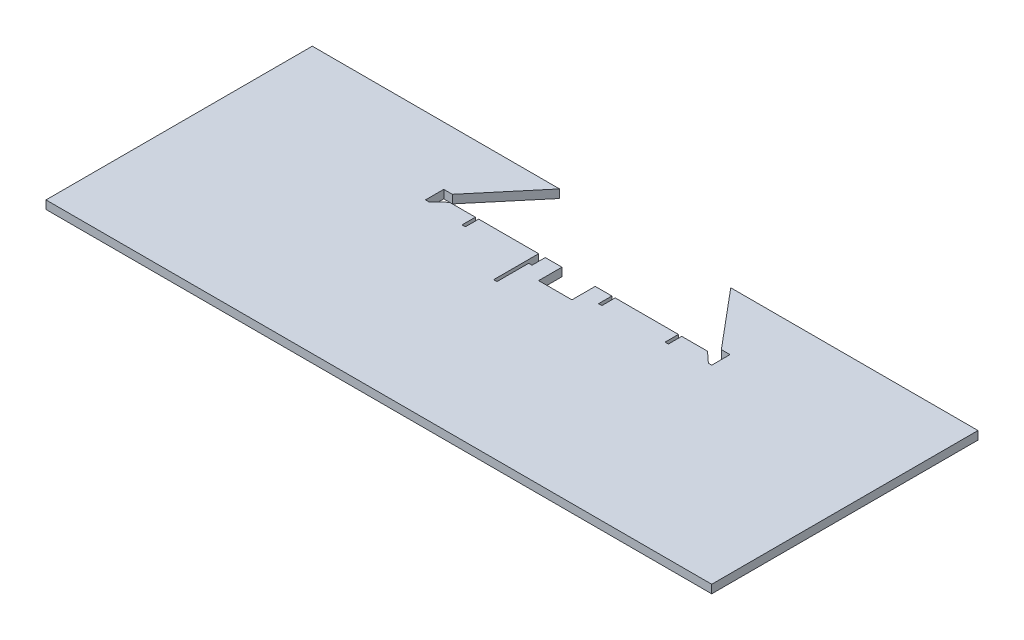
SolidWorks part; units mm, degrees
material "Depron"
ref_plane "Front Plane" through (0, 0, 0) normal (0, 0, 1) x (1, 0, 0)
ref_plane "Top Plane" through (0, 0, 0) normal (0, 1, 0) x (1, 0, 0)
ref_plane "Right Plane" through (0, 0, 0) normal (1, 0, 0) x (0, 0, -1)
sketch "Sketch1" plane through (0, 0, 0) normal (0, 1, 0) x (1, 0, 0)
  line L0 (32.6619, 101.6) -> (127, 101.6)
  line L1 (-127, 0) -> (127, 0)
  line L2 (-127, 0) -> (-127, 101.6)
  line L3 (-127, 101.6) -> (-32.6619, 101.6)
  line L4 (127, 0) -> (127, 101.6)
  line L5 (0, -898.4) -> (0, 49101.6) construction
  line L6 (-53.975, 76.2) -> (-32.6619, 101.6)
  line L7 (-53.975, 76.2) -> (53.975, 76.2)
  line L8 (53.975, 76.2) -> (32.6619, 101.6)
  line L9 (-1003.9539, 76.2) -> (48996.0461, 76.2) construction
  point P11 (0, 76.2)
  dimension "D1" = 101.6
  dimension "D2" = 254
  dimension "D4" = 107.95
  dimension "D6" = 25.4
extrude "Boss-Extrude1" add sketch "Sketch1" along normal blind 3.175
sketch "Sketch2" plane through (0, 3.175, 0) normal (0, 1, 0) x (-1, 0, 0)
  line L0 (0, 0) -> (0, -134.62) construction
  line L1 (127, 0) -> (-127, 0) construction
  line L2 (-53.975, -76.2) -> (53.975, -76.2) construction
  line L3 (39.37, -76.2) -> (38.1, -76.2)
  line L4 (39.37, -76.2) -> (39.37, -71.12)
  line L5 (39.37, -71.12) -> (38.1, -71.12)
  line L6 (38.1, -76.2) -> (38.1, -71.12)
  line L7 (13.97, -76.2) -> (12.7, -76.2)
  line L8 (-53.975, -76.2) -> (53.975, -76.2) construction
  line L9 (13.97, -71.12) -> (12.7, -71.12)
  line L10 (12.7, -76.2) -> (12.7, -71.12)
  line L11 (-12.7, -76.2) -> (-12.7, -71.12)
  line L12 (-13.97, -71.12) -> (-12.7, -71.12)
  line L13 (-13.97, -76.2) -> (-13.97, -71.12)
  line L14 (-13.97, -76.2) -> (-12.7, -76.2)
  line L15 (-38.1, -76.2) -> (-38.1, -71.12)
  line L16 (-39.37, -71.12) -> (-38.1, -71.12)
  line L17 (-39.37, -76.2) -> (-39.37, -71.12)
  line L18 (-39.37, -76.2) -> (-38.1, -76.2)
  line L19 (6.35, -76.2) -> (-6.35, -76.2)
  line L20 (13.97, -76.2) -> (15.24, -76.2)
  line L21 (13.97, -71.12) -> (13.97, -59.055)
  line L22 (13.97, -59.055) -> (15.24, -59.055)
  line L23 (15.24, -76.2) -> (15.24, -59.055)
  line L24 (6.35, -76.2) -> (6.35, -67.31)
  line L25 (6.35, -67.31) -> (-6.35, -67.31)
  line L26 (-6.35, -76.2) -> (-6.35, -67.31)
  line L27 (-53.975, -76.2) -> (-51.3109, -79.375)
  line L28 (53.34, -80.01) -> (54.61, -80.01) construction
  line L29 (53.34, -80.01) -> (53.34, -72.39) construction
  line L30 (53.34, -72.39) -> (54.61, -72.39)
  line L31 (54.61, -80.01) -> (54.61, -72.39) construction
  line L32 (53.34, -80.01) -> (54.61, -72.39) construction
  line L33 (53.34, -72.39) -> (54.61, -80.01) construction
  line L34 (-53.34, -76.2) -> (-53.975, -76.2)
  line L35 (-53.34, -72.39) -> (-49.1905, -76.2)
  line L36 (-53.34, -72.39) -> (-54.61, -72.39)
  line L37 (53.975, -76.2) -> (32.6619, -101.6) construction
  line L38 (53.975, -76.2) -> (51.3109, -79.375)
  line L39 (51.3109, -79.375) -> (54.61, -79.375)
  line L40 (54.61, -79.375) -> (54.61, -72.39)
  line L41 (53.34, -72.39) -> (49.1905, -76.2)
  line L42 (53.34, -76.2) -> (53.975, -76.2)
  line L43 (-54.61, -79.375) -> (-54.61, -72.39)
  line L44 (-51.3109, -79.375) -> (-54.61, -79.375)
  point P31 (0, -67.31)
  point P32 (53.975, -76.2)
  line M6 (-53.975, -76.2) -> (53.975, -76.2)
  line M38 (-32.6619, -101.6) -> (-53.975, -76.2)
  line M39 (53.975, -76.2) -> (32.6619, -101.6)
  dimension "D1" = 1.27
  dimension "D2" = 5.08
  dimension "D3" = 1.27
  dimension "D4" = 5.08
  dimension "D5" = 1.27
  dimension "D6" = 17.145
  dimension "D7" = 12.7
  dimension "D8" = 38.1
  dimension "D9" = 12.7
  dimension "D10" = 8.89
  dimension "D11" = 1.27
  dimension "D12" = 7.62
  dimension "D13" = 3.175
  dimension "D14" = 4.7845
ref_plane "Center Plane" through (0, 0, 0) normal (1, 0, 0) x (0, 0, -1)
sketch "Sketch3" plane through (0, 3.175, 0) normal (0, 1, 0) x (1, 0, 0)
  line L0 (-38.735, 71.12) -> (-38.735, 76.2)
  line L1 (-39.37, 71.12) -> (-38.1, 71.12) construction
  line L2 (-39.37, 76.2) -> (-38.1, 76.2) construction
  line L3 (-14.605, 76.2) -> (-14.605, 59.055)
  line L4 (-13.97, 76.2) -> (-15.24, 76.2) construction
  line L5 (-13.97, 59.055) -> (-15.24, 59.055) construction
  line L6 (-13.335, 71.12) -> (-13.335, 76.2)
  line L7 (-13.97, 71.12) -> (-12.7, 71.12) construction
  line L8 (-13.97, 76.2) -> (-12.7, 76.2) construction
  line L9 (-6.35, 76.2) -> (-6.35, 67.31)
  line L10 (-6.35, 67.31) -> (6.35, 67.31)
  line L11 (6.35, 67.31) -> (6.35, 76.2)
  line L12 (13.335, 71.12) -> (13.335, 76.2)
  line L13 (13.97, 71.12) -> (12.7, 71.12) construction
  line L14 (13.97, 76.2) -> (12.7, 76.2) construction
  line L15 (38.735, 71.12) -> (38.735, 76.2)
  line L16 (39.37, 71.12) -> (38.1, 71.12) construction
  line L17 (39.37, 76.2) -> (38.1, 76.2) construction
extrude "Cut-Extrude1" cut sketch "Sketch2" against normal up to surface (3.175 mm away) contours L6 L4 L5 M6 | L23 L22 L21 L9 L10 M6 | L26 L24 L25 M6 | L13 L11 L12 M6 | L17 L15 L16 M6 | L39 L40 L30 M6 M39 | L44 L36 L43 M38 M6 region at (52.9708, 3.175, -75.8259) region at (38.735, 3.175, -73.66) region at (13.335, 3.175, -73.66) region at (0, 3.175, -71.755) region at (-14.3147, 3.175, -69.0064) region at (-38.735, 3.175, -73.66) region at (-52.9708, 3.175, -75.8259) up to face at (0, 0, -69.85)
